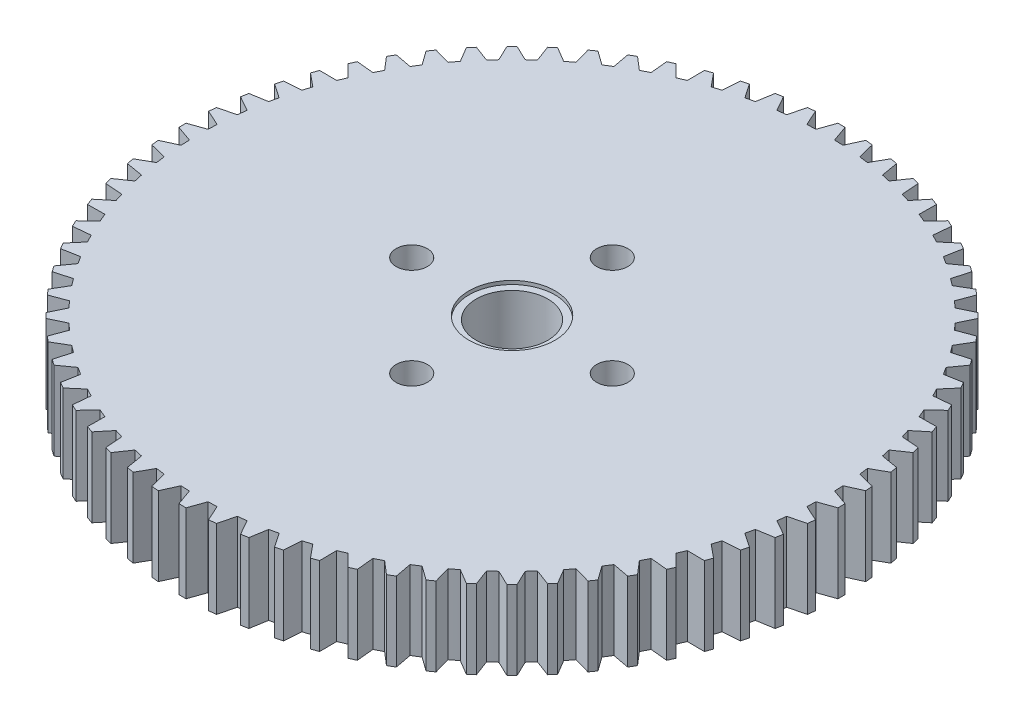
SolidWorks part; units mm, degrees
material "ABS"
ref_plane "Front" through (0, 0, 0) normal (0, 0, 1) x (1, 0, 0)
ref_plane "Top" through (0, 0, 0) normal (0, 1, 0) x (1, 0, 0)
ref_plane "Right" through (0, 0, 0) normal (1, 0, 0) x (0, 0, -1)
sketch "Sketch2" plane through (0, 0, 0) normal (0, 1, 0) x (1, 0, 0)
  circle A0 centre (0, 0) radius 21.875
  circle A1 centre (0, 0) radius 2.5
  dimension "D1" = 43.75
  dimension "D2" = 5
extrude "Boss-Extrude1" add sketch "Sketch2" along normal blind 5.5
ref_plane "Plane1" through (0, 3, 0) normal (0, 1, 0) x (1, 0, 0)
sketch "Sketch3" plane through (0, 3, 0) normal (0, 1, 0) x (1, 0, 0)
  line L0 (0, 21.875) -> (0, -21.875) construction
  line L1 (-21.875, 0) -> (21.875, 0) construction
  line L3 (0, 21.875) -> (0, 23) construction
  line L4 (-0.65, 21.8653) -> (-0.25, 23)
  line L5 (-0.25, 23) -> (0.25, 23)
  line L6 (0.65, 21.8653) -> (0.25, 23)
  circle A0 centre (0, 0) radius 21.875 construction
  arc A1 (-21.875, 0) -> (21.875, 0) centre (0, 0) ccw
  arc A2 (0.65, 21.8653) -> (-0.65, 21.8653) centre (0, 0) ccw
  dimension "D1" = 1.3
  dimension "D2" = 0.25
  dimension "D3" = 23
extrude "Boss-Extrude2" add sketch "Sketch3" along normal blind 2.5 and the other way blind 3 contours L6 L5 L4 A2
pattern_circular "CirPattern1" count 72 over 360 about axis through (0, 5.5, 0) along (0, 1, 0) of "Boss-Extrude2"
sketch "Sketch4" plane through (0, 5.5, 0) normal (0, 1, 0) x (1, 0, 0)
  circle A0 centre (0, 0) radius 3
  circle A1 centre (0, 0) radius 2.5
  circle A2 centre (0, 0) radius 2.5 construction
  dimension "D1" = 0.5
extrude "Cut-Extrude1" cut sketch "Sketch4" against normal blind 0.25
ref_plane "Plane2" through (0, 5.5, 0) normal (0, 1, 0) x (1, 0, 0)
sketch "Sketch5" plane through (0, 5.5, 0) normal (0, 1, 0) x (1, 0, 0)
  line L0 (-34.259, 0) -> (34.259, 0) construction
  line L1 (0, -34.259) -> (0, 34.259) construction
  circle A0 centre (0, 7) radius 1.09
  point P6 (0, 0)
  dimension "D1" = 7
  dimension "D2" = 2.18
extrude "Cut-Extrude2" cut sketch "Sketch5" against normal up to surface (5.5 mm away) up to face at (0, 0, 0)
pattern_circular "CirPattern2" count 4 over 360 about axis through (0, 5.25, 0) along (0, 1, 0) of "Cut-Extrude2"
